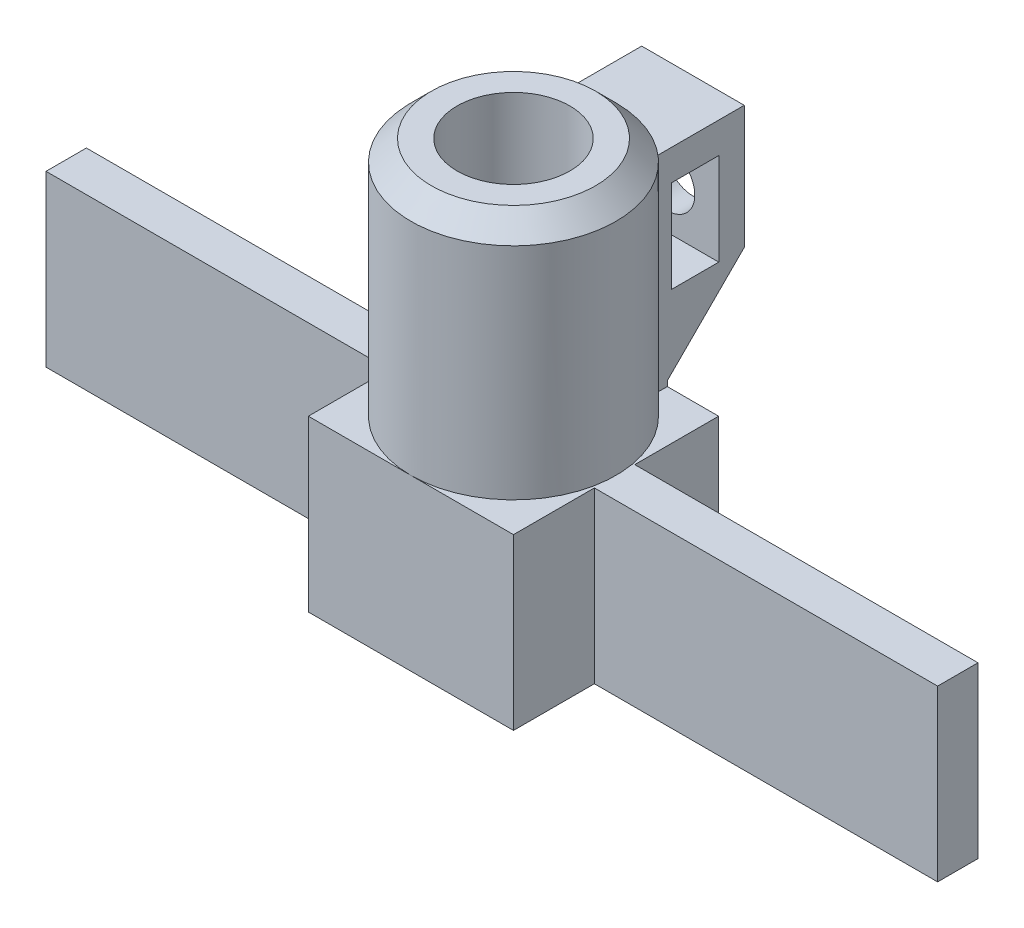
SolidWorks part; units mm, degrees
ref_plane "Front Plane" through (0, 0, 0) normal (0, 0, 1) x (1, 0, 0)
ref_plane "Top Plane" through (0, 0, 0) normal (0, 1, 0) x (1, 0, 0)
ref_plane "Right Plane" through (0, 0, 0) normal (1, 0, 0) x (0, 0, -1)
sketch "Sketch1" plane through (0, 0, 0) normal (0, 1, 0) x (1, 0, 0)
  line L1 (-12.7, -12.7) -> (12.7, -12.7)
  line L2 (-12.7, -12.7) -> (-12.7, 12.7)
  line L3 (-12.7, 12.7) -> (12.7, 12.7)
  line L4 (12.7, -12.7) -> (12.7, 12.7)
  line L5 (-12.7, -12.7) -> (12.7, 12.7) construction
  line L6 (-12.7, 12.7) -> (12.7, -12.7) construction
  point P0 (0, 0)
  dimension "D1" = 25.4
  dimension "D2" = 25.4
extrude "Boss-Extrude1" add sketch "Sketch1" along normal blind 21
sketch "Sketch8" plane through (0, 0, 12.7) normal (0, 0, 1) x (1, 0, 0)
  line L1 (0, 0) -> (-2.9028, 0)
  line L2 (0, 0) -> (0, 9.5801)
  line L3 (0, 9.5801) -> (-2.9028, 9.5801)
  line L4 (-2.9028, 0) -> (-2.9028, 9.5801)
extrude "Boss-Extrude4" add sketch "Sketch8" against normal through all
sketch "Sketch10" plane through (0, 21, 0) normal (0, 1, 0) x (1, 0, 0)
  circle A0 centre (0, 0) radius 12.7
extrude "Boss-Extrude5" add sketch "Sketch10" along normal blind 29.7815
sketch "Sketch12" plane through (0, 50.7815, 0) normal (0, 1, 0) x (1, 0, 0)
  circle A0 centre (0, 0) radius 6.985
  dimension "D1" = 13.97
extrude "Cut-Extrude2" cut sketch "Sketch12" against normal blind 22.9235
chamfer "Chamfer1" distance 2.54 angle 45 1 edges at (0, 50.7815, 12.7)
ref_plane "Plane1" through (0, 0, -6.985) normal (0, 0, 1) x (1, 0, 0)
sketch "Sketch14" plane through (0, 0, -6.985) normal (0, 0, 1) x (1, 0, 0)
  line L1 (6.35, 21) -> (-6.35, 21)
  line L2 (6.35, 21) -> (6.35, 46.4)
  line L3 (6.35, 46.4) -> (-6.35, 46.4)
  line L4 (-6.35, 21) -> (-6.35, 46.4)
  line L5 (6.35, 21) -> (-6.35, 46.4) construction
  line L6 (6.35, 46.4) -> (-6.35, 21) construction
  point P0 (0, 33.7)
  dimension "D1" = 12.7
  dimension "D2" = 25.4
  dimension "D3" = 0
extrude "Boss-Extrude6" add sketch "Sketch14" against normal blind 15.24
sketch "Sketch18" plane through (6.35, 0, 0) normal (1, 0, 0) x (0, 0, -1)
  line L1 (13.2284, 31.16) -> (19.0704, 31.16)
  line L2 (13.2284, 31.16) -> (13.2284, 42.59)
  line L3 (13.2284, 42.59) -> (19.0704, 42.59)
  line L4 (19.0704, 31.16) -> (19.0704, 42.59)
  line L5 (13.2284, 31.16) -> (19.0704, 42.59) construction
  line L6 (13.2284, 42.59) -> (19.0704, 31.16) construction
  line L7 (22.225, 46.4) -> (10.9985, 46.4) construction
  point P0 (16.1494, 36.875)
  dimension "D1" = 11.43
  dimension "D2" = 5.842
  dimension "D3" = 3.81
  dimension "D4" = 3.81
extrude "Cut-Extrude3" cut sketch "Sketch18" against normal up to next
hole_wizard "1/4 Clearance Hole2" positions "Sketch20" profile "Sketch19" hole size "1/4" standard "ANSI Inch"
sketch "Sketch20" plane through (0, 0, -22.225) normal (0, 0, -1) x (-1, 0, 0)
  line L0 (6.35, 46.4) -> (-6.35, 46.4) construction
  line L1 (-6.35, 21) -> (12.7, 21) construction
  point P0 (0, 36.875)
  dimension "D1" = 9.525
  dimension "D2" = 15.875
sketch "Sketch19" plane through (0, 36.875, -22.225) normal (1, 0, 0) x (0, 1, 0)
  line L0 (0, 0) -> (0, 22.3498)
  line L1 (0, 22.3498) -> (3.3782, 20.32)
  line L2 (3.3782, 20.32) -> (3.3782, 0)
  line L5 (3.3782, 0) -> (0, 0)
  line L10 (0, 22.3498) -> (-3.3782, 20.32) construction
  line L11 (0, -6.35) -> (0, 107.95) construction
  dimension "Hole Dia." = 6.7564
  dimension "Hole Depth" = 20.32
  dimension "Drill Angle" = 118
chamfer "Chamfer2" distance 10.16 angle 45 1 edges at (0, 21, -22.225)
sketch "Sketch21" plane through (12.7, 0, 0) normal (1, 0, 0) x (0, 0, -1)
  line L0 (0, 21) -> (12.7, 21) construction
  line L1 (-2.6836, 0) -> (2.3164, 0)
  line L2 (-2.6836, 0) -> (-2.6836, 21)
  line L3 (-2.6836, 21) -> (2.3164, 21)
  line L4 (2.3164, 0) -> (2.3164, 21)
  line L5 (-2.6836, 0) -> (2.3164, 21) construction
  line L6 (-2.6836, 21) -> (2.3164, 0) construction
  line L10 (-12.7, 0) -> (12.7, 0) construction
  point P0 (-0.1836, 10.5)
  dimension "D1" = 5
  dimension "D2" = 0
extrude "Boss-Extrude7" add sketch "Sketch21" along normal blind 42.5
sketch "Sketch22" plane through (0, 0, 0) normal (0, -1, 0) x (-1, 0, 0)
  circle A0 centre (0, 0) radius 2.64
extrude "Cut-Extrude4" cut sketch "Sketch22" against normal blind 22
mirror "Mirror1" about plane through (0, 0, 0) normal (1, 0, 0) of "Boss-Extrude7"
